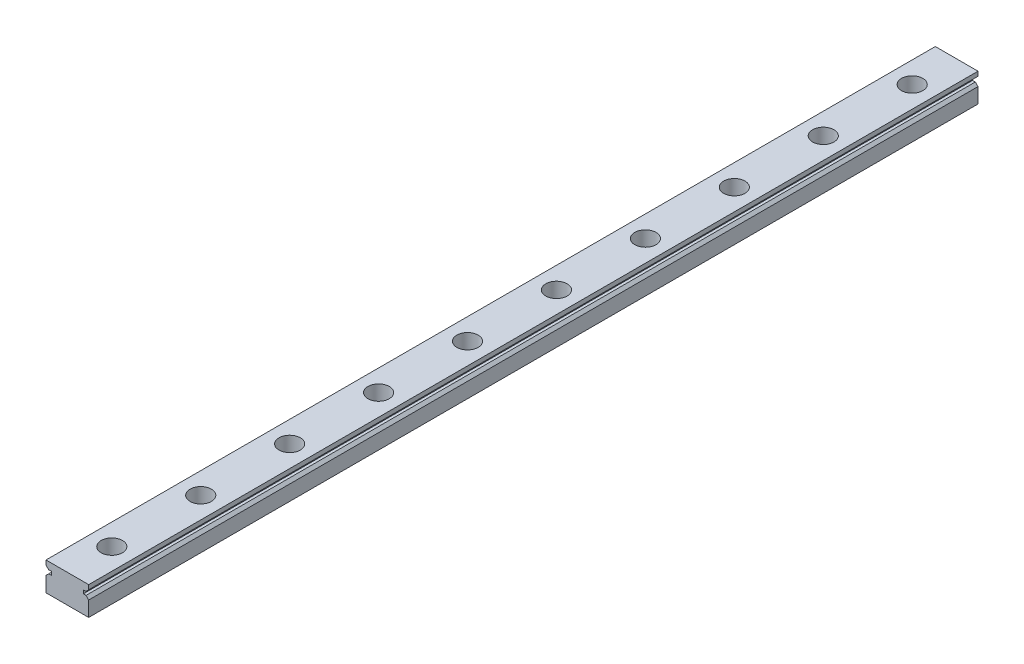
SolidWorks part; units mm, degrees
ref_plane "Front Plane" through (0, 0, 0) normal (0, 0, 1) x (1, 0, 0)
ref_plane "Top Plane" through (0, 0, 0) normal (0, 1, 0) x (1, 0, 0)
ref_plane "Right Plane" through (0, 0, 0) normal (1, 0, 0) x (0, 0, -1)
sketch "Sketch1" plane through (0, 0, 0) normal (0, 0, 1) x (1, 0, 0)
  line L0 (-6, 0) -> (6, 0)
  line L1 (6, 0) -> (6, 4.25)
  line L2 (6, 4.25) -> (5.25, 5)
  line L3 (5.25, 5) -> (4.5, 5)
  line L4 (4.5, 5) -> (4.5, 6)
  line L5 (4.5, 6) -> (5.25, 6)
  line L6 (5.25, 6) -> (6, 6.75)
  line L7 (6, 6.75) -> (6, 8)
  line L8 (6, 8) -> (-6, 8)
  line L9 (0, 0) -> (0, 8) construction
  line L10 (-6, 6.75) -> (-6, 8)
  line L11 (-5.25, 6) -> (-6, 6.75)
  line L12 (-4.5, 6) -> (-5.25, 6)
  line L13 (-4.5, 5) -> (-4.5, 6)
  line L14 (-5.25, 5) -> (-4.5, 5)
  line L15 (-6, 4.25) -> (-5.25, 5)
  line L16 (-6, 0) -> (-6, 4.25)
  point P4 (0, 0)
  dimension "D1" = 8
  dimension "D2" = 12
  dimension "D3" = 1
  dimension "D4" = 1.5
  dimension "D5" = 0.75
  dimension "D6" = 225
  dimension "D7" = 2
extrude "Boss-Extrude1" add sketch "Sketch1" along normal blind 250
sketch "Sketch2" plane through (0, 0, 0) normal (1, 0, 0) x (0, 0, -1)
  line L0 (-12.5, 0) -> (-12.5, 8) construction
  line L1 (-14.25, 0) -> (-10.75, 0) construction
  line L2 (-10.75, 0) -> (-10.75, 3.5)
  line L3 (-10.75, 3.5) -> (-9.5, 3.5)
  line L4 (-9.5, 3.5) -> (-9.5, 8)
  line L5 (-15.5, 8) -> (-9.5, 8) construction
  line L7 (-250, 0) -> (0, 0) construction
  line L8 (-250, 8) -> (0, 8) construction
  line L9 (-12.5, 8) -> (0, 8) construction
  line L10 (-12.5, 8) -> (-9.5, 8)
  line L11 (-12.5, 0) -> (-10.75, 0)
  line L12 (-12.5, 0) -> (-12.5, 8)
  point P5 (-12.5, 0)
  point P11 (-12.5, 8)
  dimension "D1" = 6
  dimension "D2" = 3.5
  dimension "D3" = 4.5
  dimension "D4" = 12.5
revolve "Cut-Revolve3" cut sketch "Sketch2" angle 360 about L12
pattern_linear "LPattern1" count 10 spacing 25 along (0, 0, 1) of "Cut-Revolve3"
